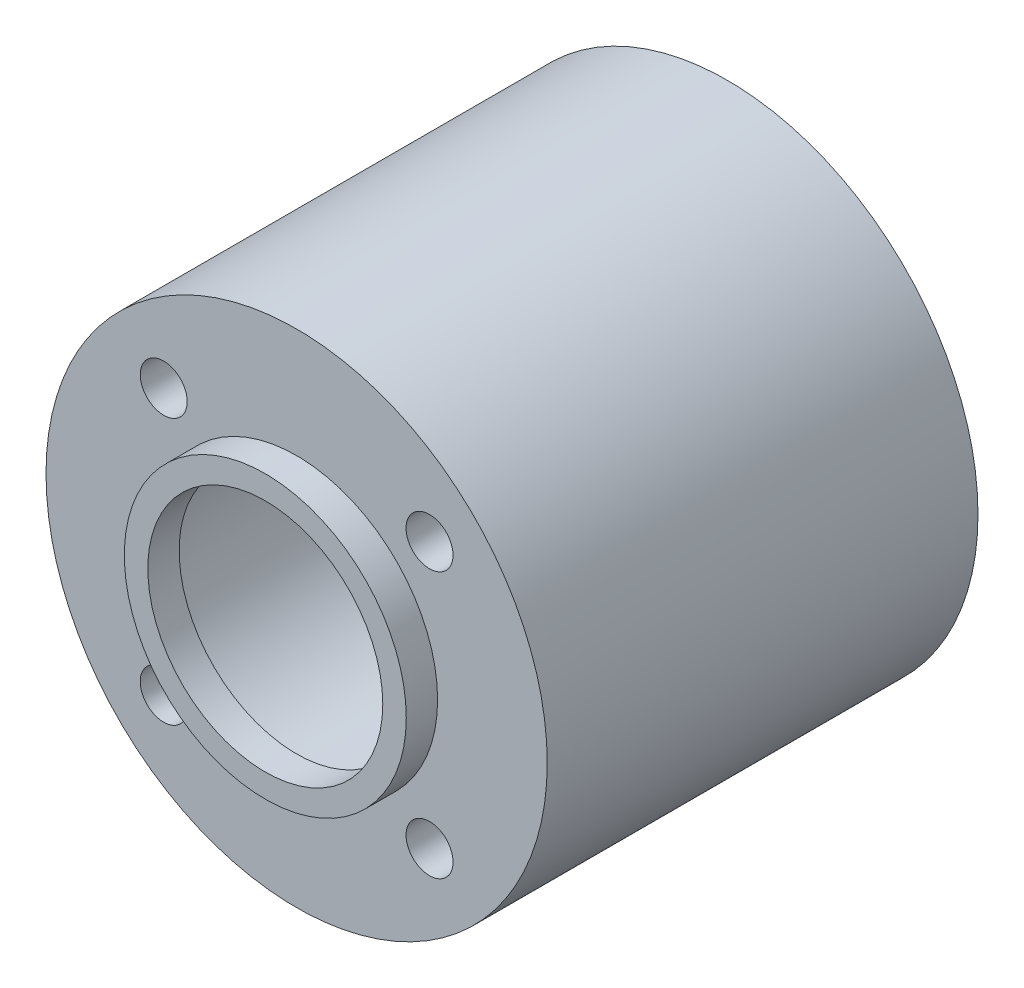
SolidWorks part; units mm, degrees
ref_plane "Front Plane" through (0, 0, 0) normal (0, 0, 1) x (1, 0, 0)
ref_plane "Top Plane" through (0, 0, 0) normal (0, 1, 0) x (1, 0, 0)
ref_plane "Right Plane" through (0, 0, 0) normal (1, 0, 0) x (0, 0, -1)
sketch "Sketch1" plane through (0, 0, 0) normal (0, 0, 1) x (1, 0, 0)
  line L0 (0, -17.575) -> (0, 17.575) construction
  line L1 (18.1737, 0) -> (-18.1737, 0) construction
  line L2 (0, 0) -> (-8.4853, 8.4853) construction
  circle A0 centre (0, 0) radius 7.5
  circle A1 centre (0, 0) radius 12 construction
  circle A2 centre (0, 0) radius 9
  circle A3 centre (0, 0) radius 16
  circle A4 centre (-8.4853, 8.4853) radius 1.5
  circle A5 centre (8.4853, 8.4853) radius 1.5
  circle A6 centre (8.4853, -8.4853) radius 1.5
  circle A7 centre (-8.4853, -8.4853) radius 1.5
  point P4 (0, 0)
  point P8 (0, 0)
  point P24 (0, 0)
  dimension "D1" = 15
  dimension "D2" = 18
  dimension "D3" = 32
  dimension "D4" = 24
  dimension "D6" = 3
  dimension "D5" = 45
  dimension "D7" = 4
extrude "Boss-Extrude1" add sketch "Sketch1" against normal blind 27.5 contours A3 A7 A6 A5 A4 A2 region at (-15.5475, 0, 0)
extrude "Boss-Extrude2" add sketch "Sketch1<3>" along normal blind 2 separate body contours A2 A0 region at (-8.7454, 0, 0)
sketch "Sketch1<3>" plane through (0, 0, 0) normal (0, 0, 1) x (1, 0, 0) same geometry as "Sketch1"
